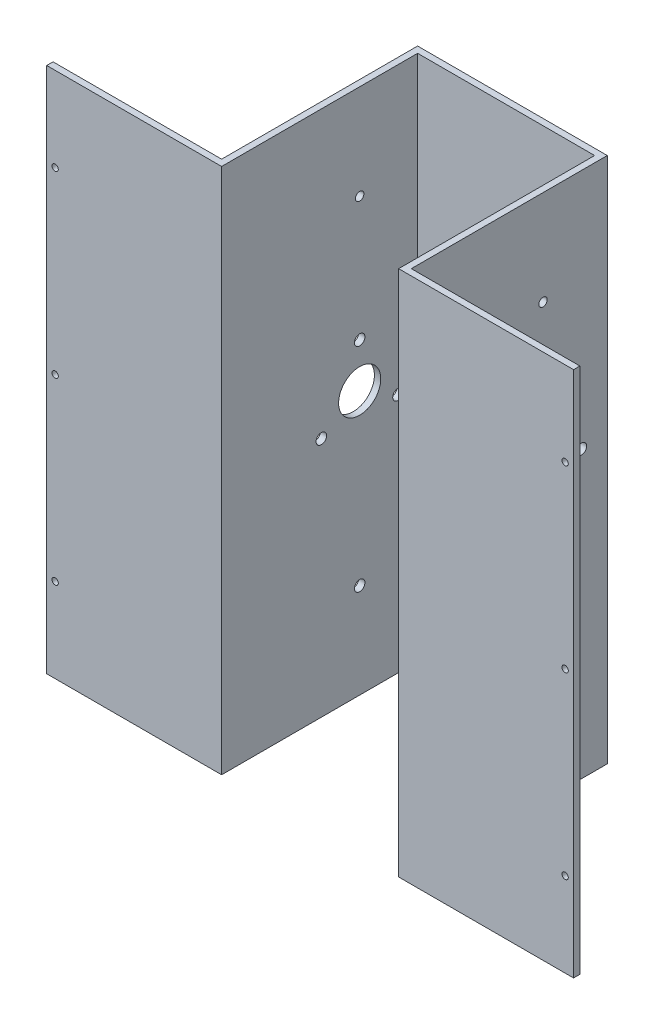
SolidWorks part; units mm, degrees
ref_plane "Plan de face" through (0, 0, 0) normal (0, 0, 1) x (1, 0, 0)
ref_plane "Plan de dessus" through (0, 0, 0) normal (0, 1, 0) x (1, 0, 0)
ref_plane "Plan de droite" through (0, 0, 0) normal (1, 0, 0) x (0, 0, -1)
sketch "Esquisse1" plane through (0, 0, 0) normal (0, 0, 1) x (1, 0, 0)
  line L1 (-24.9355, 44.0202) -> (20.0645, 44.0202)
  line L2 (-24.9355, 44.0202) -> (-24.9355, -205.9798)
  line L3 (-24.9355, -205.9798) -> (20.0645, -205.9798)
  line L4 (20.0645, 44.0202) -> (20.0645, -205.9798)
  dimension "D1" = 45
  dimension "D2" = 250
extrude "Boss.-Extru.2" add sketch "Esquisse1" along normal blind 3 contours L1 L4 L3 L2
sketch "Esquisse2" plane through (0, 0, 3) normal (0, 0, 1) x (1, 0, 0)
  line L0 (-24.9355, -205.9798) -> (20.0645, -205.9798) construction
  line L1 (-24.9355, 44.0202) -> (-21.9355, 44.0202)
  line L2 (-24.9355, 44.0202) -> (-24.9355, -205.9798)
  line L3 (-24.9355, -205.9798) -> (-21.9355, -205.9798)
  line L4 (-21.9355, 44.0202) -> (-21.9355, -205.9798)
  dimension "D1" = 3
extrude "Boss.-Extru.3" add sketch "Esquisse2" along normal blind 90
sketch "Esquisse3" plane through (0, 0, 93) normal (0, 0, 1) x (1, 0, 0)
  line L1 (-21.9355, 44.0202) -> (-104.9355, 44.0202)
  line L2 (-21.9355, 44.0202) -> (-21.9355, -205.9798)
  line L3 (-21.9355, -205.9798) -> (-104.9355, -205.9798)
  line L4 (-104.9355, 44.0202) -> (-104.9355, -205.9798)
  dimension "D1" = 250
  dimension "D2" = 83
extrude "Boss.-Extru.4" add sketch "Esquisse3" along normal blind 3
sketch "Esquisse4" plane through (-24.9355, 0, 0) normal (-1, 0, 0) x (0, 0, 1)
  line L0 (0, -80.9798) -> (169.8773, -80.9798) construction
  line L1 (0, 44.0202) -> (0, -205.9798) construction
  line L2 (30.5, -80.9798) -> (12.3135, -91.4798) construction
  line L3 (30.5, -115.9798) -> (30.5, -228.1916) construction
  line L4 (30.5, -80.9798) -> (30.5, -59.9798) construction
  line L5 (30.5, 61.8433) -> (30.5, -90.9798) construction
  line L6 (30.5, -80.9798) -> (-21.1236, -110.7847) construction
  circle A0 centre (30.5, -80.9798) radius 10
  circle A1 centre (30.5, -59.9798) radius 2.5
  circle A2 centre (48.6865, -91.4798) radius 2.5
  circle A4 centre (30.5, -80.9798) radius 35
  circle A5 centre (30.5, -0.9798) radius 35
  circle A6 centre (30.5, -160.9798) radius 35
  circle A7 centre (30.5, -0.9798) radius 2
  circle A8 centre (30.5, -160.9798) radius 2.5
  circle A9 centre (12.3135, -91.4798) radius 2.5
  dimension "D1" = 20
  dimension "D2" = 30.5
  dimension "D4" = 120
  dimension "D8" = 70
  dimension "D9" = 70
  dimension "D10" = 70
  dimension "D11" = 80
  dimension "D12" = 80
  dimension "D13" = 4
  dimension "D14" = 5
  dimension "D16" = 5
  dimension "D17" = 21
  dimension "D3" = 3
  dimension "D15" = 30
extrude "Enlèv. mat.-Extru.1" cut sketch "Esquisse4" against normal blind 3 contours A7 | A0 | A8 | A1 | A9 | A2 region at (-24.9355, -80.9798, 30.5) region at (-24.9355, -59.9798, 30.5) region at (-24.9355, -91.4798, 48.6865) region at (-24.9355, -0.9798, 30.5) region at (-24.9355, -160.9798, 30.5) region at (-24.9355, -91.4798, 12.3135)
sketch "Esquisse5" plane through (0, 0, 96) normal (0, 0, 1) x (1, 0, 0)
  line L0 (-104.9355, -80.9798) -> (108.8881, -80.9798) construction
  line L1 (-89.9355, 39.0202) -> (-159.7076, 39.0202)
  line L2 (-89.9355, 39.0202) -> (-89.9355, -30.9798)
  line L3 (-89.9355, -30.9798) -> (-159.7076, -30.9798)
  line L4 (-159.7076, 39.0202) -> (-159.7076, -30.9798)
  line L5 (-89.9355, -45.9798) -> (-159.7076, -45.9798)
  line L6 (-89.9355, -45.9798) -> (-89.9355, -115.9798)
  line L7 (-89.9355, -115.9798) -> (-159.7076, -115.9798)
  line L8 (-159.7076, -45.9798) -> (-159.7076, -115.9798)
  line L9 (-89.9355, -130.9798) -> (-159.7076, -130.9798)
  line L10 (-89.9355, -130.9798) -> (-89.9355, -200.9798)
  line L11 (-89.9355, -200.9798) -> (-159.7076, -200.9798)
  line L12 (-159.7076, -130.9798) -> (-159.7076, -200.9798)
  line L13 (-104.9355, 44.0202) -> (-104.9355, -205.9798) construction
  circle A0 centre (-100.9355, 4.0202) radius 1.5
  circle A1 centre (-100.9355, -80.9798) radius 1.5
  circle A2 centre (-100.9355, -165.9798) radius 1.5
  dimension "D10" = 3
  dimension "D11" = 3
  dimension "D12" = 3
  dimension "D13" = 4
  dimension "D14" = 4
  dimension "D15" = 4
  dimension "D1" = 70
  dimension "D2" = 70
  dimension "D3" = 70
  dimension "D4" = 35
  dimension "D5" = 15
  dimension "D6" = 15
  dimension "D7" = 15
  dimension "D8" = 15
  dimension "D9" = 15
extrude "Enlèv. mat.-Extru.2" cut sketch "Esquisse5" against normal blind 3 contours A1 L0 | L0 A1 | A2 | A0 region at (-100.9355, -80.3432, 96) region at (-100.9355, -81.6164, 96) region at (-100.9355, -165.9798, 96)
mirror "Symétrie1" about plane through (20.0645, 44.0202, 3) normal (1, 0, 0) of "Enlèv. mat.-Extru.2", "Boss.-Extru.4", "Boss.-Extru.3", "Boss.-Extru.2"
sketch "Esquisse6" plane through (65.0645, 0, 0) normal (1, 0, 0) x (0, 0, -1)
  line L0 (-30.5, -80.9798) -> (-12.3135, -70.4798) construction
  line L2 (-30.5, -80.9798) -> (-30.5, -101.9798) construction
  line L4 (-30.5, -80.9798) -> (30.6923, -80.9798) construction
  line L5 (-30.5, -80.9798) -> (18.7655, -52.5364) construction
  circle A0 centre (-30.5, -80.9798) radius 10
  circle A1 centre (-30.5, -0.9798) radius 2
  circle A2 centre (-30.5, -160.9798) radius 2.5
  circle A3 centre (-30.5, -101.9798) radius 2.5
  circle A4 centre (-48.6865, -70.4798) radius 2.5
  circle A6 centre (-12.3135, -70.4798) radius 2.5
  dimension "D2" = 120
  dimension "D7" = 5
  dimension "D8" = 21
  dimension "D1" = 3
  dimension "D6" = 30
extrude "Enlèv. mat.-Extru.3" cut sketch "Esquisse6" against normal blind 3
